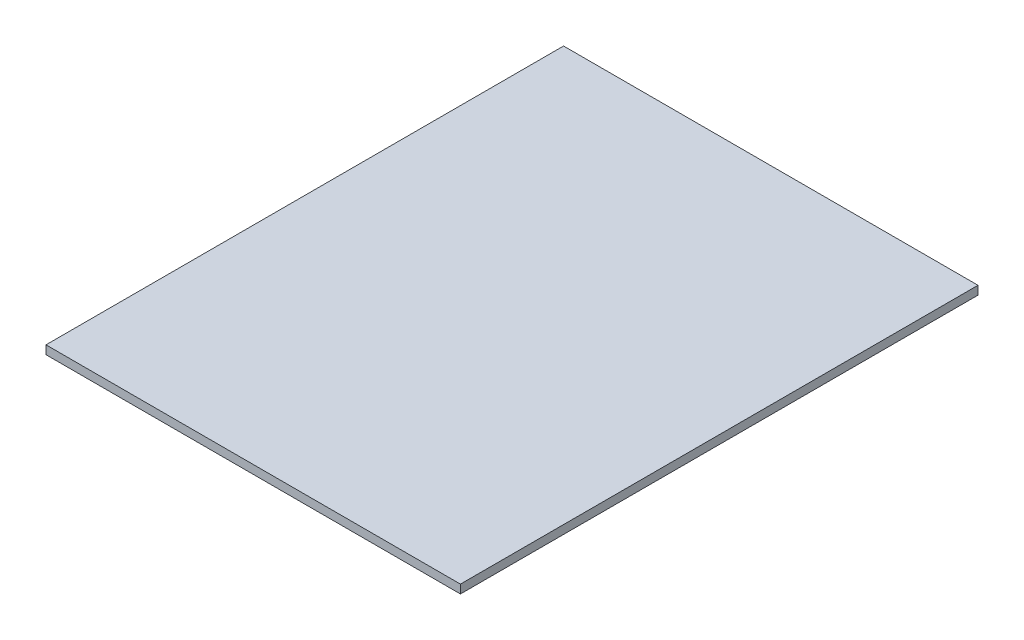
SolidWorks part; units mm, degrees
ref_plane "Front Plane" through (0, 0, 0) normal (0, 0, 1) x (1, 0, 0)
ref_plane "Top Plane" through (0, 0, 0) normal (0, 1, 0) x (1, 0, 0)
ref_plane "Right Plane" through (0, 0, 0) normal (1, 0, 0) x (0, 0, -1)
sketch "Sketch1" plane through (0, 0, 0) normal (0, 1, 0) x (1, 0, 0)
  line L1 (0, 0) -> (144.93, 0)
  line L2 (0, 0) -> (0, 181)
  line L3 (0, 181) -> (144.93, 181)
  line L4 (144.93, 0) -> (144.93, 181)
  dimension "D1" = 181
  dimension "D2" = 144.93
extrude "Boss-Extrude1" add sketch "Sketch1" along normal blind 3
